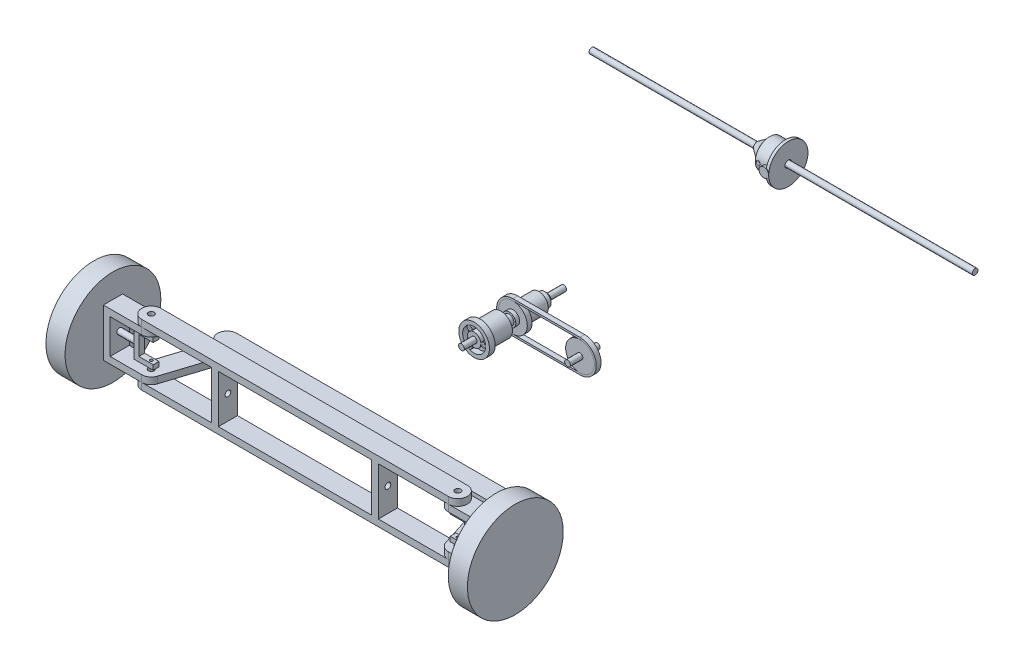
SolidWorks part; units mm, degrees
other "RD Pinion"
other "RD Ring Gear"
other "RD L Gear Right"
other "RD L Gear Left"
other "RD S Gear Outer"
other "RD S Gear Inner"
other "RD S Gear Inner"
other "Tie Plate"
other "Front Right Knuckle"
other "Front Left Knuckle"
other "Front Plate"
other "Main Shaft"
other "Front Right Wheel"
other "Front Left Wheel"
ref_plane "Front Plane" through (0, 0, 0) normal (0, 0, 1) x (1, 0, 0)
ref_plane "Top Plane" through (0, 0, 0) normal (0, 1, 0) x (1, 0, 0)
ref_plane "Right Plane" through (0, 0, 0) normal (1, 0, 0) x (0, 0, -1)
sketch "Top View Layout" plane through (0, 0, 0) normal (0, 1, 0) x (1, 0, 0)
  line L0 (-100, 125) -> (100, 125)
  line L1 (0, 125) -> (0, -125)
  line L2 (-100, -125) -> (100, -125)
  line L3 (0, -15) -> (35, -15) construction
  line L4 (35, -15) -> (35, -125) construction
  line L5 (2.5, 114.75) -> (2.5, 135.25) construction
  line L6 (-2.5, 114.75) -> (2.5, 114.75) construction
  line L7 (-8.75, 127) -> (-2.75, 127) construction
  line L8 (-2.5, 114.75) -> (2.5, 114.75) construction
  line L9 (-2.5, 114.75) -> (-2.5, 116.25) construction
  line L10 (-2.5, 116.25) -> (2.5, 116.25) construction
  line L11 (2.5, 114.75) -> (2.5, 116.25) construction
  line L12 (2.5, 135.25) -> (1, 135.25) construction
  line L13 (2.5, 135.25) -> (2.5, 114.75) construction
  line L14 (2.5, 114.75) -> (1, 114.75) construction
  line L15 (1, 135.25) -> (1, 114.75) construction
  line L16 (-4.25, 128.5) -> (-2.75, 128.5) construction
  line L17 (-4.25, 128.5) -> (-4.25, 121.5) construction
  line L18 (-4.25, 121.5) -> (-2.75, 121.5) construction
  line L19 (-2.75, 128.5) -> (-2.75, 121.5) construction
  line L20 (-4.25, 128.5) -> (-2.75, 121.5) construction
  line L21 (-4.25, 121.5) -> (-2.75, 128.5) construction
  line L22 (-8.75, 128.5) -> (-7.25, 128.5) construction
  line L23 (-8.75, 128.5) -> (-8.75, 121.5) construction
  line L24 (-8.75, 121.5) -> (-7.25, 121.5) construction
  line L25 (-7.25, 128.5) -> (-7.25, 121.5) construction
  line L26 (-8.75, 128.5) -> (-7.25, 121.5) construction
  line L27 (-8.75, 121.5) -> (-7.25, 128.5) construction
  line L28 (-8.75, 123) -> (-2.75, 123) construction
  line L29 (-5.75, 123) -> (-5.75, 120.2863) construction
  line L30 (-5.75, 127) -> (-5.75, 129.2691) construction
  point P8 (0, 114.75)
  point P9 (0, 0)
  point P11 (2.5, 125)
  point P16 (2.5, 125)
  point P19 (0, 114.75)
  point P23 (-3.5, 125)
  point P28 (-8, 125)
  point P41 (0, 0)
  dimension "D1" = 250
  dimension "D2" = 200
  dimension "D3" = 35
  dimension "D4" = 15
  dimension "D5" = 5
  dimension "D6" = 20.5
  dimension "D7" = 1.5
  dimension "D8" = 1.5
  dimension "D9" = 1.5
  dimension "D10" = 7
  dimension "D11" = 3.5
  dimension "D12" = 8
  dimension "D13" = 1.5
  dimension "D14" = 1.5
ref_plane "Left" through (100, 0, 0) normal (-1, 0, 0) x (0, 0, 1)
ref_plane "Right" through (-100, 0, 0) normal (-1, 0, 0) x (0, 0, 1)
sketch "Left Wheels" plane through (100, 0, 0) normal (-1, 0, 0) x (0, 0, 1)
  circle A0 centre (125, 0) radius 25
  circle A1 centre (-125, 0) radius 25
  point P4 (0, 0)
  dimension "D1" = 50
  dimension "D2" = 50
sketch "Right Wheels" plane through (-100, 0, 0) normal (-1, 0, 0) x (0, 0, 1)
  circle A0 centre (-125, 0) radius 25 construction
  circle A1 centre (125, 0) radius 25 construction
  circle A2 centre (-125, 0) radius 25
  circle A3 centre (125, 0) radius 25
ref_plane "Rear Differential Pinion Plane" through (0, 0, -114.75) normal (0, 0, 1) x (1, 0, 0)
sketch "Rear Differential Pinion Profile" plane through (0, 0, -114.75) normal (0, 0, 1) x (1, 0, 0)
  circle A0 centre (0, 0) radius 2.5
ref_plane "Rear Differential Ring Gear Plane" through (2.5, 0, 0) normal (1, 0, 0) x (0, 0, -1)
ref_plane "Rear Axle" through (0, 0, -125) normal (0, 0, 1) x (1, 0, 0)
sketch "Rear Differential Ring Gear Profile" plane through (2.5, 0, 0) normal (1, 0, 0) x (0, 0, -1)
  line L0 (114.75, 0) -> (135.25, 0) construction
  circle A0 centre (125, 0) radius 10.25
extrude "Rear Differential Pinion" add sketch "Rear Differential Pinion Profile" against normal blind 1.5 contours A0
extrude "Rear Differential Ring Gear" add sketch "Rear Differential Ring Gear Profile" against normal blind 1.5 separate body contours A0
ref_plane "RD Inner L Gear Plane" through (-2.75, 0, 0) normal (1, 0, 0) x (0, 0, -1)
ref_plane "RD Outer L Gear Plane" through (-8.75, 0, 0) normal (1, 0, 0) x (0, 0, -1)
sketch "RD Inner L Gear Profile" plane through (-2.75, 0, 0) normal (1, 0, 0) x (0, 0, -1)
  circle A0 centre (125, 0) radius 3.5
sketch "RD Outer L Gear Profile" plane through (-8.75, 0, 0) normal (1, 0, 0) x (0, 0, -1)
  line L0 (128.5, 0) -> (121.5, 0) construction
  circle A0 centre (125, 0) radius 3.5
ref_plane "RD Inner S Gear Plane" through (0, 0, -121.5) normal (0, 0, 1) x (1, 0, 0)
ref_plane "RD Outer S Gear Plane" through (0, 0, -128.5) normal (0, 0, 1) x (1, 0, 0)
sketch "RD Inner S Gear Profile" plane through (0, 0, -121.5) normal (0, 0, 1) x (1, 0, 0)
  line L0 (-8.75, 0) -> (-7.25, 0) construction
  circle A0 centre (-5.75, 0) radius 3
sketch "RD Outer S Gear Profile" plane through (0, 0, -128.5) normal (0, 0, 1) x (1, 0, 0)
  line L0 (-8.75, 0) -> (-7.25, 0) construction
  circle A2 centre (-5.75, 0) radius 3
extrude "RD Outer L Gear Extrude" add sketch "RD Outer L Gear Profile" along normal blind 1.5 separate body contours A0
extrude "RD Inner L Gear Extrude" add sketch "RD Inner L Gear Profile" against normal blind 1.5 separate body contours A0
extrude "RD Outer S Gear Extrude" add sketch "RD Outer S Gear Profile" along normal blind 1.5 separate body contours A2
extrude "RD Inner S Gear Extrude" add sketch "RD Inner S Gear Profile" against normal blind 1.5 separate body contours A0
sketch "RD Ring Gear Case Profile" plane through (1, 0, 0) normal (-1, 0, 0) x (0, 0, 1)
  line L0 (-121.5, 3.2113) -> (-121.5, -3.2113)
  line L1 (-128.5, 3.2113) -> (-128.5, -3.2113)
  line L2 (-121.5, 6.6332) -> (-121.5, 3.2113) construction
  line L3 (-128.5, 6.6332) -> (-128.5, 3.2113) construction
  line L4 (-121.5, -3.2113) -> (-121.5, -6.6332) construction
  line L5 (-128.5, -3.2113) -> (-128.5, -6.6332) construction
  circle A0 centre (-125, 0) radius 7.5
  arc A1 (-121.5, 3.2113) -> (-128.5, 3.2113) centre (-125, 0) ccw
  arc A2 (-121.5, -3.2113) -> (-121.5, 3.2113) centre (-125, 0) ccw construction
  arc A3 (-128.5, 3.2113) -> (-128.5, -3.2113) centre (-125, 0) ccw construction
  arc A4 (-128.5, -3.2113) -> (-121.5, -3.2113) centre (-125, 0) ccw
  point P7 (-121.5, 0)
  dimension "D1" = 15
  dimension "D2" = 9.5
extrude "RD Ring Gear Case " add sketch "RD Ring Gear Case Profile" along normal blind 8.25
sketch "Sketch11" plane through (-7.25, 0, 0) normal (-1, 0, 0) x (0, 0, 1)
  circle A0 centre (-125, 0) radius 5.5
  circle A1 centre (-125, 0) radius 4.75
  arc A2 (-121.5, 3.2113) -> (-128.5, 3.2113) centre (-125, 0) ccw construction
  dimension "D1" = 11
extrude "Boss-Extrude8" add sketch "Sketch11" along normal up to vertex up to point (-8.75, 0, -128.5)
fillet "Fillet1" radius 2 1 edges at (-7.25, 0, -119.5)
sketch "Sketch12" plane through (0, 0, -125) normal (0, 0, 1) x (1, 0, 0)
  line L0 (-8.75, 0) -> (-13.75, 0) construction
  line L1 (-8.75, 0) -> (-7.25, 0) construction
  line L2 (-8.75, 0) -> (-7.25, 0) construction
  line L3 (-100, 0) -> (100, 0) construction
  line L4 (-100, 0) -> (100, 0) construction
  line L5 (-8.75, 5.5) -> (-8.75, -5.5) construction
  line L6 (-13.75, 0) -> (-13.75, 2)
  line L7 (-13.75, 2) -> (-8.75, 5.5)
  line L8 (-13.75, 0) -> (-8.75, 0)
  line L9 (-8.75, 0) -> (-8.75, 5.5)
  point P15 (-13.75, 1)
  dimension "D1" = 5
  dimension "D2" = 2
revolve "Revolve1" add sketch "Sketch12" angle 360 about L0
sketch "Sketch13" plane through (2.5, 0, 0) normal (1, 0, 0) x (0, 0, -1)
  circle A0 centre (125, 0) radius 1.75
  dimension "D1" = 3.5
extrude "Cut-Extrude1" cut sketch "Sketch13" against normal through all
sketch "Sketch14" plane through (0, 0, -121.5) normal (0, 0, 1) x (1, 0, 0)
  circle A0 centre (-5.75, 0) radius 1
  dimension "D1" = 2
extrude "Boss-Extrude9" add sketch "Sketch14" along normal blind 4
sketch "Sketch15" plane through (0, 0, -121.5) normal (0, 0, 1) x (1, 0, 0)
  circle A0 centre (-5.75, 0) radius 1.1
  dimension "D1" = 2.2
extrude "Cut-Extrude2" cut sketch "Sketch15" against normal through all both and the other way through all
extrude "Boss-Extrude10" add sketch "Sketch14<2>" against normal blind 4 from surface starting at face at (-2.75, 0, -128.5)
sketch "Sketch14<2>" plane through (0, 0, -121.5) normal (0, 0, 1) x (1, 0, 0) same geometry as "Sketch14"
sketch "Sketch16" plane through (-8.75, 0, 0) normal (-1, 0, 0) x (0, 0, 1)
  circle A0 centre (-125, 0) radius 1.5
  dimension "D1" = 3
extrude "Boss-Extrude11" add sketch "Sketch16" along normal up to vertex (91.25 mm away) up to point (-100, 0, -125)
sketch "Sketch17" plane through (-2.75, 0, 0) normal (1, 0, 0) x (0, 0, -1)
  circle A0 centre (125, 0) radius 1.5 construction
  circle A1 centre (125, 0) radius 1.5
extrude "Boss-Extrude12" add sketch "Sketch17" along normal up to vertex (102.75 mm away) up to point (100, 0, -125)
sketch "Transfer Case Layout" plane through (0, 0, 0) normal (0, 1, 0) x (1, 0, 0)
  line L0 (0, 125) -> (0, -125) construction
  line L1 (-7.5, -13.75) -> (7.5, -13.75)
  line L2 (-7.5, -13.75) -> (-7.5, -16.25)
  line L3 (-7.5, -16.25) -> (7.5, -16.25)
  line L4 (7.5, -13.75) -> (7.5, -16.25)
  line L5 (-7.5, -13.75) -> (7.5, -16.25) construction
  line L6 (-7.5, -16.25) -> (7.5, -13.75) construction
  line L7 (27.5, -13.75) -> (42.5, -13.75)
  line L8 (27.5, -13.75) -> (27.5, -16.25)
  line L9 (27.5, -16.25) -> (42.5, -16.25)
  line L10 (42.5, -13.75) -> (42.5, -16.25)
  line L11 (27.5, -13.75) -> (42.5, -16.25) construction
  line L12 (27.5, -16.25) -> (42.5, -13.75) construction
  line L13 (2.5, -17.25) -> (-2.5, -17.25)
  line L14 (2.5, -17.25) -> (2.5, -16.25)
  line L15 (2.5, -16.25) -> (-2.5, -16.25)
  line L16 (-2.5, -17.25) -> (-2.5, -16.25)
  line L17 (2.5, -17.25) -> (-2.5, -16.25) construction
  line L18 (2.5, -16.25) -> (-2.5, -17.25) construction
  line L19 (-2, -4.75) -> (-2, -10.75)
  line L20 (3.5, -18.25) -> (-3.5, -18.25)
  line L21 (3.5, -18.25) -> (3.5, -16.25)
  line L22 (3.5, -16.25) -> (-3.5, -16.25)
  line L23 (-3.5, -18.25) -> (-3.5, -16.25)
  line L24 (3.5, -18.25) -> (-3.5, -16.25) construction
  line L25 (3.5, -16.25) -> (-3.5, -18.25) construction
  line L26 (2.5, -20) -> (-2.5, -20)
  line L27 (2.5, -20) -> (2.5, -17.5)
  line L28 (2.5, -17.5) -> (-2.5, -17.5)
  line L29 (-2.5, -20) -> (-2.5, -17.5)
  line L30 (2.5, -20) -> (-2.5, -17.5) construction
  line L31 (2.5, -17.5) -> (-2.5, -20) construction
  line L32 (-3.5, -9.25) -> (3.5, -9.25)
  line L33 (-3.5, -9.25) -> (-3.5, -10.75)
  line L34 (-3.5, -10.75) -> (3.5, -10.75)
  line L35 (3.5, -9.25) -> (3.5, -10.75)
  line L36 (-3.5, -9.25) -> (3.5, -10.75) construction
  line L37 (-3.5, -10.75) -> (3.5, -9.25) construction
  line L38 (-3.5, -4.75) -> (3.5, -4.75)
  line L39 (-3.5, -4.75) -> (-3.5, -6.25)
  line L40 (-3.5, -6.25) -> (3.5, -6.25)
  line L41 (3.5, -4.75) -> (3.5, -6.25)
  line L42 (-3.5, -4.75) -> (3.5, -6.25) construction
  line L43 (-3.5, -6.25) -> (3.5, -4.75) construction
  line L44 (2, -4.75) -> (2, -10.75)
  line L45 (0, -6.25) -> (0, -9.25) construction
  line L46 (-5, -2.75) -> (5, -2.75) construction
  line L47 (-5, -2.75) -> (-5, -12.75) construction
  line L48 (-5, -12.75) -> (5, -12.75) construction
  line L49 (5, -2.75) -> (5, -12.75) construction
  line L50 (-5, -2.75) -> (5, -12.75) construction
  line L51 (-5, -12.75) -> (5, -2.75) construction
  line L52 (-6, -22.5) -> (-6, -24)
  line L53 (-2.5, -1.75) -> (2.5, -1.75)
  line L54 (-2.5, -1.75) -> (-2.5, -2.75)
  line L55 (-2.5, -2.75) -> (2.5, -2.75)
  line L56 (2.5, -1.75) -> (2.5, -2.75)
  line L57 (-2.5, -1.75) -> (2.5, -2.75) construction
  line L58 (-2.5, -2.75) -> (2.5, -1.75) construction
  line L59 (-2.5, 1.25) -> (2.5, 1.25)
  line L60 (-2.5, 1.25) -> (-2.5, -0.75)
  line L61 (-2.5, -0.75) -> (2.5, -0.75)
  line L62 (2.5, 1.25) -> (2.5, -0.75)
  line L63 (-2.5, 1.25) -> (2.5, -0.75) construction
  line L64 (-2.5, -0.75) -> (2.5, 1.25) construction
  line L65 (3.5, 0.25) -> (-3.5, 0.25)
  line L66 (3.5, 0.25) -> (3.5, -2.25)
  line L67 (3.5, -2.25) -> (-3.5, -2.25)
  line L68 (-3.5, 0.25) -> (-3.5, -2.25)
  line L69 (3.5, 0.25) -> (-3.5, -2.25) construction
  line L70 (3.5, -2.25) -> (-3.5, 0.25) construction
  line L71 (-2.5, -22.5) -> (2.5, -22.5)
  line L72 (-2.5, -22.5) -> (-2.5, -27.5)
  line L73 (-2.5, -27.5) -> (2.5, -27.5)
  line L74 (2.5, -22.5) -> (2.5, -27.5)
  line L75 (-2.5, -22.5) -> (2.5, -27.5) construction
  line L76 (-2.5, -27.5) -> (2.5, -22.5) construction
  line L77 (-6, -24) -> (6, -24)
  line L78 (6, -24) -> (6, -22.5)
  line L79 (6, -22.5) -> (-6, -22.5)
  line L80 (-4.5, -22.5) -> (-4.5, -24)
  line L81 (4.5, -22.5) -> (4.5, -24)
  line L82 (-6, -24) -> (-6, -33.5) construction
  line L83 (2.5, -29.5) -> (-2.5, -29.5)
  line L84 (2.5, -29.5) -> (2.5, -28)
  line L85 (2.5, -28) -> (-2.5, -28)
  line L86 (-2.5, -29.5) -> (-2.5, -28)
  line L87 (2.5, -29.5) -> (-2.5, -28) construction
  line L88 (2.5, -28) -> (-2.5, -29.5) construction
  line L89 (-4.5, -26.5) -> (4.5, -26.5)
  line L90 (-4.5, -26.5) -> (-4.5, -29.5)
  line L91 (-4.5, -29.5) -> (4.5, -29.5)
  line L92 (4.5, -26.5) -> (4.5, -29.5)
  line L93 (-4.5, -26.5) -> (4.5, -29.5) construction
  line L94 (-4.5, -29.5) -> (4.5, -26.5) construction
  line L95 (6, -24) -> (6, -33.5) construction
  line L96 (-3.5, -33.5) -> (-3.5, -36.5)
  line L97 (6, -36.5) -> (-6, -36.5)
  line L98 (6, -36.5) -> (6, -33.5)
  line L99 (6, -33.5) -> (-6, -33.5)
  line L100 (-6, -36.5) -> (-6, -33.5)
  line L101 (6, -36.5) -> (-6, -33.5) construction
  line L102 (6, -33.5) -> (-6, -36.5) construction
  line L103 (3.5, -33.5) -> (3.5, -36.5)
  line L104 (0, -28) -> (0, -43.1129)
  line L109 (8, -36.5) -> (-8, -36.5)
  line L110 (8, -36.5) -> (8, -33.5)
  line L111 (8, -33.5) -> (-8, -33.5)
  line L112 (-8, -36.5) -> (-8, -33.5)
  line L113 (8, -36.5) -> (-8, -33.5) construction
  line L114 (8, -33.5) -> (-8, -36.5) construction
  line L115 (0, -27.5) -> (0, -9.25)
  line L116 (0, -6.25) -> (0, -1.75)
  line L117 (0, -0.75) -> (0, 11.0375)
  line L118 (35, -22.7597) -> (35, -7.2403)
  point P0 (0, -15)
  point P6 (35, -15)
  point P12 (0, -16.75)
  point P19 (0, -17.25)
  point P24 (0, -18.75)
  point P29 (0, -10)
  point P34 (0, -5.5)
  point P43 (0, -7.75)
  point P50 (0, -2.25)
  point P55 (0, 0.25)
  point P60 (0, -1)
  point P65 (0, -25)
  point P72 (0, -22.5)
  point P79 (0, -28.75)
  point P84 (0, -28)
  point P92 (0, -35)
  point P98 (0, -35)
  point P99 (0, -35)
  point P113 (35, -15)
  dimension "D1" = 2.5
  dimension "D2" = 2.5
  dimension "D3" = 15
  dimension "D4" = 15
  dimension "D5" = 1
  dimension "D6" = 5
  dimension "D7" = 7
  dimension "D8" = 2
  dimension "D9" = 0.25
  dimension "D10" = 2.5
  dimension "D11" = 7
  dimension "D12" = 5
  dimension "D13" = 1.5
  dimension "D14" = 1.5
  dimension "D15" = 1.5
  dimension "D16" = 1.5
  dimension "D17" = 6
  dimension "D18" = 2
  dimension "D19" = 1.5
  dimension "D20" = 5
  dimension "D21" = 1
  dimension "D22" = 2
  dimension "D23" = 1
  dimension "D24" = 7
  dimension "D25" = 2.5
  dimension "D26" = 0.5
  dimension "D27" = 5
  dimension "D28" = 5
  dimension "D29" = 10
  dimension "D30" = 1.5
  dimension "D31" = 12
  dimension "D32" = 1.5
  dimension "D33" = 1.5
  dimension "D34" = 1.5
  dimension "D35" = 0.5
  dimension "D36" = 3
  dimension "D37" = 3
  dimension "D38" = 20
  dimension "D39" = 2.5
  dimension "D40" = 2.5
  dimension "D41" = 7
  dimension "D42" = 2
  dimension "D43" = 16
ref_plane "FWD Sprocket Plane" through (0, 0, 15) normal (0, 0, 1) x (1, 0, 0)
sketch "Sketch19" plane through (0, 0, 15) normal (0, 0, 1) x (1, 0, 0)
  circle A0 centre (35, 0) radius 7.5
  circle A1 centre (0, 0) radius 7.5
  point P6 (7.5, 0)
  point P9 (27.5, 0)
extrude "FWD Sprockets" add sketch "Sketch19" along normal up to vertex (1.25 mm away) and the other way up to vertex (1.25 mm away) separate body up to point (-7.5, 0, 16.25) other way up to point (-7.5, 0, 13.75)
sketch "Sketch20" plane through (0, 0, 15) normal (0, 0, 1) x (1, 0, 0)
  line L0 (0, 8.5) -> (35, 8.5)
  line L1 (0, -8.5) -> (35, -8.5)
  line L2 (0, 7.5) -> (35, 7.5)
  line L3 (0, -7.5) -> (35, -7.5)
  circle A0 centre (0, 0) radius 7.5 construction
  arc A1 (0, 7.5) -> (0, -7.5) centre (0, 0) ccw
  circle A2 centre (35, 0) radius 7.5 construction
  arc A3 (35, -7.5) -> (35, 7.5) centre (35, 0) ccw
  arc A4 (0, 8.5) -> (0, -8.5) centre (0, 0) ccw
  arc A5 (35, -8.5) -> (35, 8.5) centre (35, 0) ccw
  arc A6 (4, -7.5) -> (4, 7.5) centre (0, 0) ccw construction
  arc A7 (0, -7.5) -> (0, 7.5) centre (0, 0) ccw construction
  arc A8 (35, 7.5) -> (35, -7.5) centre (35, 0) ccw construction
  arc A9 (31, 7.5) -> (31, -7.5) centre (35, 0) ccw construction
  arc A10 (4, 7.5) -> (0, 8.5) centre (0, 0) ccw construction
  arc A11 (35, 8.5) -> (31, 7.5) centre (35, 0) ccw construction
  arc A12 (31, -7.5) -> (35, -8.5) centre (35, 0) ccw construction
  arc A13 (0, -8.5) -> (4, -7.5) centre (0, 0) ccw construction
  dimension "D1" = 1
  dimension "D2" = 1
extrude "FWD Sprocket Chain" add sketch "Sketch20" along normal up to surface and the other way up to surface separate body up to face at (7.5, 0, 16.25) other way up to face at (7.5, 0, 13.75)
sketch "Sketch21" plane through (0, 0, 16.25) normal (0, 0, 1) x (1, 0, 0)
  circle A0 centre (0, 0) radius 2.5
  point P3 (2.5, 0)
extrude "FWD Sprocket Dog Gear" add sketch "Sketch21" along normal up to vertex (1 mm away) up to point (-2.5, 0, 17.25)
ref_plane "Mode Sleeve Gear Plane" through (0, 0, 18.25) normal (0, 0, 1) x (1, 0, 0)
sketch "Sketch22" plane through (0, 0, 18.25) normal (0, 0, 1) x (1, 0, 0)
  circle A0 centre (0, 0) radius 3.5
  circle A1 centre (0, 0) radius 2.5 construction
  circle A2 centre (0, 0) radius 2.5
extrude "Mode Sleeve Gear" add sketch "Sketch22" against normal up to vertex (2 mm away) separate body up to point (3.5, 0, 16.25)
sketch "Sketch23" plane through (0, 0, 18.25) normal (0, 0, 1) x (1, 0, 0)
  circle A0 centre (0, 0) radius 2.5 construction
  circle A1 centre (0, 0) radius 2.5
extrude "Mode Sleeve Main Shaft Gear" add sketch "Sketch23" along normal up to vertex (1.75 mm away) and the other way up to vertex (0.75 mm away) separate body up to point (2.5, 0, 20) other way up to point (2.5, 0, 17.5)
ref_plane "Range Sleeve Rear Plane" through (0, 0, 22.5) normal (0, 0, 1) x (1, 0, 0)
sketch "Sketch24" plane through (0, 0, 22.5) normal (0, 0, 1) x (1, 0, 0)
  circle A0 centre (0, 0) radius 2.5
extrude "Main Shaft Range Sleeve Gear" add sketch "Sketch24" along normal up to vertex (5 mm away) separate body up to point (-2.5, 0, 27.5)
sketch "Sketch25" plane through (0, 0, 22.5) normal (0, 0, 1) x (1, 0, 0)
  circle A0 centre (0, 0) radius 6
  circle A3 centre (0, 0) radius 4.5
extrude "Carrier Range Sleeve Gear" add sketch "Sketch25" along normal up to vertex (1.5 mm away) separate body up to point (6, 0, 24)
ref_plane "Range Sleeve Input Shaft Side" through (0, 0, 29.5) normal (0, 0, 1) x (1, 0, 0)
sketch "Sketch27" plane through (0, 0, 29.5) normal (0, 0, 1) x (1, 0, 0)
  circle A0 centre (0, 0) radius 2.5
extrude "Input Range Sleeve Gear" add sketch "Sketch27" against normal up to vertex (1.5 mm away) separate body up to point (2.5, 0, 28)
sketch "Sketch28" plane through (0, 0, 29.5) normal (0, 0, 1) x (1, 0, 0)
  circle A0 centre (0, 0) radius 4.5
  circle A1 centre (0, 0) radius 2.5 construction
  circle A2 centre (0, 0) radius 2.5
extrude "Range Sleeve Sleeve Gear" add sketch "Sketch28" against normal up to vertex (3 mm away) separate body up to point (4.5, 0, 26.5)
ref_plane "Planetary Input Side Plane" through (0, 0, 36.5) normal (0, 0, 1) x (1, 0, 0)
sketch "Sketch29" plane through (0, 0, 36.5) normal (0, 0, 1) x (1, 0, 0)
  circle A0 centre (0, 0) radius 3.5
extrude "Planetary Sun Gear" add sketch "Sketch29" against normal up to vertex (3 mm away) separate body up to point (3.5, 0, 33.5)
sketch "Sketch30" plane through (0, 0, 36.5) normal (0, 0, 1) x (1, 0, 0)
  line L0 (6, 0) -> (-6, 0) construction
  circle A0 centre (4.75, 0) radius 1.25
extrude "Planetary Planet Gear" add sketch "Sketch30" against normal up to vertex (3 mm away) separate body up to point (6, 0, 33.5)
pattern_circular "Planetary Planet Gear x 3" count 3 over 360 about axis through (0, 0, 28) along (0, 0, 1) reverse direction yes of bodies 132
sketch "Sketch31" plane through (0, 0, 36.5) normal (0, 0, 1) x (1, 0, 0)
  circle A0 centre (0, 0) radius 6
  circle A1 centre (0, 0) radius 8
extrude "Planetary Ring Gear" add sketch "Sketch31" against normal up to vertex (3 mm away) separate body up to point (8, 0, 33.5)
ref_plane "Planetary Rear Side Plane" through (0, 0, 33.5) normal (0, 0, 1) x (1, 0, 0)
sketch "Sketch32" plane through (0, 0, 33.5) normal (0, 0, 1) x (1, 0, 0)
  line L0 (3.5, 0) -> (6, 0) construction
  line L1 (0, 0) -> (4.75, 0) construction
  line L2 (0, 0) -> (-2.375, -4.1136) construction
  circle A0 centre (0, 0) radius 6
  circle A1 centre (4.75, 0) radius 0.5
  circle A2 centre (-2.375, -4.1136) radius 0.5
  circle A3 centre (-2.375, 4.1136) radius 0.5
  point P4 (4.75, 0)
  dimension "D1" = 1
  dimension "D3" = 120
  dimension "D4" = 4.75
  dimension "D2" = 3
extrude "Carrier" add sketch "Sketch32" against normal blind 1 separate body contours A3 | A0 A3 A2 A1 | A1 | A2 region at (0, 0, 33.5) region at (4.75, 0, 33.5) region at (-2.375, -4.1136, 33.5) region at (-2.375, 4.1136, 33.5)
extrude "Carrier Shafts" add sketch "Sketch32<3>" along normal up to vertex (3 mm away) contours A1 | A2 | A3 region at (4.75, 0, 33.5) region at (-2.375, -4.1136, 33.5) up to point (-3.5, 0, 36.5)
sketch "Sketch32<3>" plane through (0, 0, 33.5) normal (0, 0, 1) x (1, 0, 0) same geometry as "Sketch32"
sketch "Sketch33" plane through (0, 0, 33.5) normal (0, 0, 1) x (1, 0, 0)
  circle A0 centre (0, 0) radius 6 construction
  circle A1 centre (0, 0) radius 6
  circle A2 centre (0, 0) radius 5.5
  dimension "D1" = 0.5
extrude "Carrier Range Sleeve Gear Connect" add sketch "Sketch33" against normal up to surface (9.5 mm away) up to face at (6, 0, 24)
ref_plane "Center Diff Main Shaft Sidegear Plane" through (0, 0, 10.75) normal (0, 0, 1) x (1, 0, 0)
sketch "Sketch34" plane through (0, 0, 10.75) normal (0, 0, 1) x (1, 0, 0)
  circle A0 centre (0, 0) radius 3.5
extrude "Center Diff Main Shaft Side Gear" add sketch "Sketch34" against normal up to vertex (1.5 mm away) separate body up to point (3.5, 0, 9.25)
ref_plane "Center Diff Rear Shaft Sidegear Plane" through (0, 0, 4.75) normal (0, 0, 1) x (1, 0, 0)
ref_plane "Center Diff Mid Plane" through (0, 0, 7.75) normal (0, 0, 1) x (1, 0, 0)
mirror "Center Diff Rear Shaft Side Gear" about plane through (0, 0, 7.75) normal (0, 0, 1) of bodies 139
ref_plane "Center Diff Right Pinion Inner Plane" through (-2, 0, 0) normal (-1, 0, 0) x (0, 0, 1)
sketch "Sketch35" plane through (-2, 0, 0) normal (-1, 0, 0) x (0, 0, 1)
  line L0 (4.75, 0) -> (10.75, 0) construction
  circle A0 centre (7.75, 0) radius 3
extrude "Center Diff Right Pinion" add sketch "Sketch35" along normal up to vertex (1.5 mm away) separate body up to point (-3.5, 0, 10.75)
ref_plane "Center Diff Left Side Pinion Inner Plane" through (2, 0, 0) normal (-1, 0, 0) x (0, 0, 1)
sketch "Sketch36" plane through (2, 0, 0) normal (-1, 0, 0) x (0, 0, 1)
  line L0 (4.75, 0) -> (10.75, 0) construction
  circle A0 centre (7.75, 0) radius 3
extrude "Center Diff Left Pinion" add sketch "Sketch36" against normal up to vertex (1.5 mm away) separate body up to point (3.5, 0, 4.75)
ref_plane "Center Diff Rear Shaft Side Plane" through (0, 0, 2.75) normal (0, 0, 1) x (1, 0, 0)
sketch "Sketch37" plane through (0, 0, 2.75) normal (0, 0, 1) x (1, 0, 0)
  circle A0 centre (0, 0) radius 5
extrude "Center Diff Rear Axle Side Plate" add sketch "Sketch37" along normal up to vertex (2 mm away) separate body up to point (3.5, 0, 4.75)
mirror "Center Diff Main Shaft Side Plate" about plane through (0, 0, 7.75) normal (0, 0, 1) of bodies 143
sketch "Sketch38" plane through (0, 0, 2.75) normal (0, 0, 1) x (1, 0, 0)
  line L0 (3.5, -2.8284) -> (3.5, 2.8284)
  line L1 (-3.4263, -2.9173) -> (-3.5, -2.8284)
  line L2 (-3.5, -2.8284) -> (-3.5, 2.8284)
  circle A0 centre (0, 0) radius 5 construction
  circle A1 centre (0, 0) radius 5
  arc A2 (3.5, 2.8284) -> (-3.5, 2.8284) centre (0, 0) ccw
  arc A3 (3.5, -2.8284) -> (3.5, 2.8284) centre (0, 0) ccw construction
  arc A4 (-3.5, 2.8284) -> (-3.5, -2.8284) centre (0, 0) ccw construction
  arc A5 (-3.5, -2.8284) -> (3.5, -2.8284) centre (0, 0) ccw
  dimension "D1" = 0.5
extrude "Center Diff Case" add sketch "Sketch38" along normal up to surface (8 mm away) contours A1 A5 L2 A2 L0 region at (-4.8586, 0, 2.75) up to face at (5, 0, 10.75)
sketch "Sketch39" plane through (0, 0, 2.75) normal (0, 0, 1) x (1, 0, 0)
  circle A0 centre (0, 0) radius 2.5
extrude "Center Diff Lock Gear" add sketch "Sketch39" against normal up to vertex (1 mm away) up to point (2.5, 0, 1.75)
ref_plane "Lock Sleeve Plane" through (0, 0, -0.25) normal (0, 0, 1) x (1, 0, 0)
sketch "Sketch41" plane through (0, 0, -0.25) normal (0, 0, 1) x (1, 0, 0)
  circle A0 centre (0, 0) radius 3.5
  circle A1 centre (0, 0) radius 2.5 construction
  circle A2 centre (0, 0) radius 2.5
extrude "Lock Sleeve" add sketch "Sketch41" along normal up to vertex (2.5 mm away) separate body up to point (-3.5, 0, 2.25)
sketch "Sketch42" plane through (0, 0, -0.25) normal (0, 0, 1) x (1, 0, 0)
  circle A0 centre (0, 0) radius 2.5 construction
  circle A1 centre (0, 0) radius 2.5
extrude "Lock Sleeve Rear Shaft Gear" add sketch "Sketch42" along normal up to vertex (1 mm away) and the other way up to vertex (1 mm away) separate body up to point (2.5, 0, 0.75) other way up to point (2.5, 0, -1.25)
sketch "Sketch43" plane through (-2, 0, 0) normal (-1, 0, 0) x (0, 0, 1)
  line L0 (4.75, 0) -> (10.75, 0) construction
  circle A0 centre (7.75, 0) radius 0.5
  dimension "D1" = 1
extrude "Center Diff Pinion Rotation Point Cut" cut sketch "Sketch43" against normal through all both and the other way through all
sketch "Sketch45" plane through (0, 0, 2.75) normal (0, 0, 1) x (1, 0, 0)
  circle A0 centre (0, 0) radius 0.5
  dimension "D1" = 1
extrude "Center Diff Side Gear Rotation Point" cut sketch "Sketch45" against normal through all both and the other way through all
sketch "Sketch46" plane through (0, 0, -0.25) normal (0, 0, 1) x (1, 0, 0)
  circle A0 centre (0, 0) radius 1.5
  dimension "D1" = 3
extrude "Rear Shaft" add sketch "Sketch46" along normal up to vertex (1 mm away) and the other way blind 10 up to point (0, 0, 0.75)
sketch "Sketch47" plane through (0, 0, 2.75) normal (0, 0, 1) x (1, 0, 0)
  circle A0 centre (0, 0) radius 0.5
  dimension "D1" = 1
extrude "Center Diff Rear Shaft Side Axle" add sketch "Sketch47" along normal up to vertex (3.5 mm away) and the other way up to vertex (1 mm away) up to point (0, 0, 6.25) other way up to point (0, 0, 1.75)
sketch "Sketch48" plane through (-2, 0, 0) normal (-1, 0, 0) x (0, 0, 1)
  circle A0 centre (7.75, 0) radius 0.5 construction
  circle A1 centre (7.75, 0) radius 0.5
extrude "Center Diff Right Side Pinion Axle" add sketch "Sketch48" along normal up to vertex (3 mm away) up to point (-5, 0, 12.75)
sketch "Sketch49" plane through (2, 0, 0) normal (-1, 0, 0) x (0, 0, 1)
  circle A0 centre (7.75, 0) radius 0.5 construction
  circle A1 centre (7.75, 0) radius 0.5
extrude "Center Diff Left Side Pinion Axle" add sketch "Sketch49" against normal up to vertex (3 mm away) up to point (5, 0, 2.75)
sketch "Sketch50" plane through (0, 0, 18.25) normal (0, 0, 1) x (1, 0, 0)
  circle A0 centre (0, 0) radius 0.5
  dimension "D1" = 1
extrude "Main Shaft Sprocket Rotation Point Cut" cut sketch "Sketch50" against normal through all both and the other way through all
extrude "Main Shaft Extrude" add sketch "Sketch50<2>" against normal up to vertex (9 mm away) and the other way up to vertex (9.25 mm away) up to point (0, 0, 9.25) other way up to point (0, 0, 27.5)
sketch "Sketch50<2>" plane through (0, 0, 18.25) normal (0, 0, 1) x (1, 0, 0) same geometry as "Sketch50"
sketch "Sketch52" plane through (0, 0, 36.5) normal (0, 0, 1) x (1, 0, 0)
  circle A0 centre (0, 0) radius 1.5
  dimension "D1" = 3
extrude "Input Shaft Carrier Cut" cut sketch "Sketch52" against normal through all both and the other way through all
extrude "Input Shaft" add sketch "Sketch52<2>" along normal up to vertex (6.6129 mm away) and the other way up to vertex (8.5 mm away) up to point (0, 0, 43.1129) other way up to point (0, 0, 28)
sketch "Sketch52<2>" plane through (0, 0, 36.5) normal (0, 0, 1) x (1, 0, 0) same geometry as "Sketch52"
sketch "Sketch54" plane through (0, 0, 15) normal (0, 0, 1) x (1, 0, 0)
  circle A0 centre (35, 0) radius 1.5
  dimension "D1" = 3
extrude "FW Shaft" add sketch "Sketch54" along normal up to vertex (7.7597 mm away) and the other way up to vertex (7.7597 mm away) up to point (35, 0, 22.7597) other way up to point (35, 0, 7.2403)
sketch "Steering Layout" plane through (0, 0, 0) normal (0, 1, 0) x (1, 0, 0)
  line L0 (0, 125) -> (80, -125) construction
  line L1 (-100, -125) -> (100, -125) construction
  line L2 (-80, -125) -> (0, 125) construction
  line L3 (-80, -125) -> (-70.4, -95)
  line L4 (-70.4, -95) -> (70.4, -95)
  line L5 (70.4, -95) -> (80, -125)
  dimension "D1" = 20
  dimension "D2" = 20
  dimension "D3" = 30
ref_plane "Y + 12.5mm" through (0, 12.5, 0) normal (0, 1, 0) x (1, 0, 0)
ref_plane "Y - 12.5mm" through (0, -12.5, 0) normal (0, 1, 0) x (1, 0, 0)
sketch "Front Plate Profile" plane through (0, 12.5, 0) normal (0, 1, 0) x (1, 0, 0)
  line L0 (-80, -120) -> (80, -120)
  line L1 (80, -130) -> (-80, -130)
  circle A0 centre (-80, -125) radius 1.5
  arc A1 (-80, -120) -> (-80, -130) centre (-80, -125) ccw
  circle A2 centre (80, -125) radius 1.5
  arc A3 (80, -130) -> (80, -120) centre (80, -125) ccw
  arc A4 (-80, -130) -> (-80, -120) centre (-80, -125) ccw construction
  arc A5 (80, -120) -> (80, -130) centre (80, -125) ccw construction
  point P12 (0, 0)
  point P13 (0, 0)
  dimension "D1" = 3
  dimension "D2" = 10
  dimension "D3" = 3
  dimension "D4" = 10
extrude "Upper Plate" add sketch "Front Plate Profile" along normal blind 3.5 separate body
mirror "Lower Plate" about plane through (0, 0, 0) normal (0, 1, 0) of bodies 164
sketch "Upper and Lower Plate Connect Profile" plane through (0, 12.5, 0) normal (0, 1, 0) x (1, 0, 0)
  line L0 (80, -120) -> (-80, -120) construction
  line L1 (40, -120) -> (43.5, -120)
  line L2 (40, -120) -> (40, -130)
  line L3 (40, -130) -> (43.5, -130)
  line L4 (43.5, -120) -> (43.5, -130)
  line L5 (-80, -130) -> (80, -130) construction
  line L6 (0, -120) -> (0, -130) construction
  line L7 (-43.5, -120) -> (-43.5, -130)
  line L8 (-40, -130) -> (-43.5, -130)
  line L9 (-40, -120) -> (-40, -130)
  line L10 (-40, -120) -> (-43.5, -120)
  point P11 (0, 0)
  point P12 (0, 0)
  dimension "D1" = 3.5
  dimension "D2" = 5
extrude "Upper and Lower Plate Connect" add sketch "Upper and Lower Plate Connect Profile" against normal up to surface (25 mm away) up to face at (0, -12.5, 125)
sketch "Front Axle Profile" plane through (0, 0, 0) normal (1, 0, 0) x (0, 0, -1)
  circle A0 centre (-125, 0) radius 1.5
  point P2 (0, 0)
  dimension "D1" = 3
extrude "Front Plate Front Axis Hole" cut sketch "Front Axle Profile" against normal through all both and the other way through all
sketch "Steering Knuckle Top Profile" plane through (0, 12.5, 0) normal (0, 1, 0) x (1, 0, 0)
  line L0 (80, -120) -> (100, -120)
  line L1 (100, -120) -> (100, -130)
  line L2 (100, -130) -> (80, -130)
  circle A0 centre (80, -125) radius 1.5 construction
  circle A1 centre (80, -125) radius 1.5
  arc A2 (80, -120) -> (80, -130) centre (80, -125) ccw
  arc A4 (80, -130) -> (80, -120) centre (80, -125) ccw construction
  dimension "D1" = 10
extrude "Top Steering Knuckle" add sketch "Steering Knuckle Top Profile" against normal blind 3.5 separate body
mirror "Bottom Steering Knuckle" about plane through (0, 0, 0) normal (0, 1, 0) of bodies 168
sketch "Steering Knuckle Side Profile" plane through (0, -9, 0) normal (0, 1, 0) x (1, 0, 0)
  line L0 (80, -130) -> (100, -130) construction
  line L1 (100, -120) -> (96.5, -120)
  line L2 (100, -120) -> (100, -130)
  line L3 (100, -130) -> (96.5, -130)
  line L4 (96.5, -120) -> (96.5, -130)
  dimension "D1" = 3.5
extrude "Steering Knuckle Side" add sketch "Steering Knuckle Side Profile" along normal up to surface (18 mm away) up to face at (80, 9, 126.5)
sketch "Steering Knuckle Shaft Profile" plane through (100, 0, 0) normal (1, 0, 0) x (0, 0, -1)
  circle A0 centre (-125, 0) radius 1.5
  dimension "D1" = 3
extrude "Steering Knuckle Shaft Cut" cut sketch "Steering Knuckle Shaft Profile" against normal through all both and the other way through all
sketch "Steering Knuckle Four Bar Profile" plane through (0, -9, 0) normal (0, 1, 0) x (1, 0, 0)
  line L0 (65.6379, -96.5239) -> (75.2379, -126.5239)
  line L1 (75.1621, -93.4761) -> (84.7621, -123.4761)
  arc A0 (75.1621, -93.4761) -> (65.6379, -96.5239) centre (70.4, -95) ccw
  circle A1 centre (70.4, -95) radius 1.5
  arc A2 (80, -120) -> (80, -130) centre (80, -125) ccw construction
  arc A3 (75.2379, -126.5239) -> (84.7621, -123.4761) centre (80, -125) ccw
  circle A4 centre (80, -125) radius 1.5 construction
  circle A5 centre (80, -125) radius 1.5
  arc A6 (65.6379, -96.5239) -> (75.1621, -93.4761) centre (70.4, -95) ccw construction
  arc A7 (84.7621, -123.4761) -> (75.2379, -126.5239) centre (80, -125) ccw construction
  dimension "D1" = 10
  dimension "D2" = 3
extrude "Steering Knuckle Four Bar" add sketch "Steering Knuckle Four Bar Profile" against normal up to surface (3.5 mm away) up to face at (80, -12.5, 126.5)
mirror "Steering Knuckle Mirror" about plane through (0, 0, 0) normal (1, 0, 0) of bodies 173 171
sketch "Tie Plate Profile" plane through (0, -9, 0) normal (0, 1, 0) x (1, 0, 0)
  line L0 (-70.4, -100) -> (70.4, -100)
  line L1 (-70.4, -90) -> (70.4, -90)
  arc A0 (70.4, -100) -> (70.4, -90) centre (70.4, -95) ccw
  arc A1 (75.1621, -93.4761) -> (65.6379, -96.5239) centre (70.4, -95) ccw construction
  arc A2 (-70.4, -90) -> (-70.4, -100) centre (-70.4, -95) ccw
  arc A3 (-65.6379, -96.5239) -> (-75.1621, -93.4761) centre (-70.4, -95) ccw construction
  circle A4 centre (70.4, -95) radius 1.5 construction
  circle A5 centre (-70.4, -95) radius 1.5 construction
  circle A6 centre (70.4, -95) radius 1.5
  circle A7 centre (-70.4, -95) radius 1.5
  arc A8 (-70.4, -100) -> (-70.4, -90) centre (-70.4, -95) ccw construction
  arc A9 (70.4, -90) -> (70.4, -100) centre (70.4, -95) ccw construction
  arc M8 (75.1621, -93.4761) -> (65.6379, -96.5239) centre (70.4, -95) ccw
  line M9 (65.6379, -96.5239) -> (75.2379, -126.5239)
  circle M14 centre (70.4, -95) radius 1.5
extrude "Tie Plate Extrude" add sketch "Tie Plate Profile" along normal blind 3.5 separate body contours A7 | M14 | L1 A2 L0 A7 M9 M8 | L0 A0 M8 M9 M14 region at (-3.7176, -9, 94.9924) region at (66.3288, -9, 98.2188) region at (70.4, -9, 95) region at (-70.4, -9, 95)
extrude "Tie Plate Attachment Bits" add sketch "Sketch63<3>" against normal blind 3.5 contours A7 | A6 region at (-70.4, -9, 95)
sketch "Sketch63<3>" plane through (0, -9, 0) normal (0, 1, 0) x (1, 0, 0) same geometry as "Tie Plate Profile"
ref_plane "L Wheel" through (100, 0, 0) normal (1, 0, 0) x (0, 0, -1)
sketch "Front Wheel Profile" plane through (100, 0, 0) normal (1, 0, 0) x (0, 0, -1)
  circle A0 centre (-125, 0) radius 25 construction
  circle A1 centre (-125, 0) radius 25
  circle A2 centre (-125, 0) radius 1.5 construction
  circle A3 centre (-125, 0) radius 1.5
extrude "Front Wheel" add sketch "Front Wheel Profile" along normal blind 10 separate body contours A3 | A1 A3 region at (100, 0, 149.2929) region at (100, 0, 125)
sketch "Front Wheel Shaft Profile" plane through (100, 0, 0) normal (1, 0, 0) x (0, 0, -1)
  circle A0 centre (-125, 0) radius 1.5 construction
  circle A1 centre (-125, 0) radius 1.5
extrude "Front Wheel Shaft" add sketch "Front Wheel Shaft Profile" against normal blind 15
ref_plane "Front Axle" through (0, 0, 125) normal (0, 0, 1) x (1, 0, 0)
sketch "Wheel U Joint Profile" plane through (0, 0, 125) normal (0, 0, 1) x (1, 0, 0)
  line L0 (85, 1.5) -> (85, -1.5) construction
  line L1 (85, 1.5) -> (85, -1.5)
  line L2 (-100, 0) -> (100, 0) construction
  line L3 (85, 7.5) -> (87.5, 7.5)
  line L4 (85, 5) -> (85, -5)
  line L5 (85, -7.5) -> (87.5, -7.5)
  line L6 (87.5, 7.5) -> (87.5, -7.5)
  line L7 (-100, 0) -> (100, 0) construction
  line L8 (87.5, 0) -> (63.8298, 0) construction
  line L9 (87.5, 7.5) -> (77.5, 7.5)
  line L10 (87.5, 7.5) -> (87.5, 5)
  line L11 (85, 5) -> (77.5, 5)
  line L12 (77.5, 7.5) -> (77.5, 5)
  line L13 (85, -5) -> (77.5, -5)
  line L14 (77.5, -7.5) -> (77.5, -5)
  line L15 (87.5, -7.5) -> (77.5, -7.5)
  line L16 (85, 7.5) -> (85, 5) construction
  line L17 (87.5, 5) -> (85, 5) construction
  line L18 (85, -5) -> (85, -7.5) construction
  line L19 (87.5, -5) -> (85, -5) construction
  point P22 (77.5, -7.5)
  point P23 (85, -7.5)
  dimension "D1" = 2.5
  dimension "D2" = 7.5
  dimension "D3" = 7.5
  dimension "D4" = 2.5
  dimension "D5" = 10
extrude "Wheel U Joint" add sketch "Wheel U Joint Profile" along normal blind 1.5 and the other way blind 1.5 contours L15 L5 L6 L3 L9 L12 L11 L4 L1 L13 L14 region at (85.1803, 3.25, 125)
sketch "Wheel U Joint Shaft Holes Profile" plane through (0, 7.5, 0) normal (0, 1, 0) x (1, 0, 0)
  circle A1 centre (80, -125) radius 0.75
  dimension "D1" = 1.5
extrude "Wheel U Joint Shaft Holes" cut sketch "Wheel U Joint Shaft Holes Profile" against normal through all both and the other way through all
mirror "Wheel Mirror" about plane through (0, 0, 0) normal (1, 0, 0) of bodies 179
